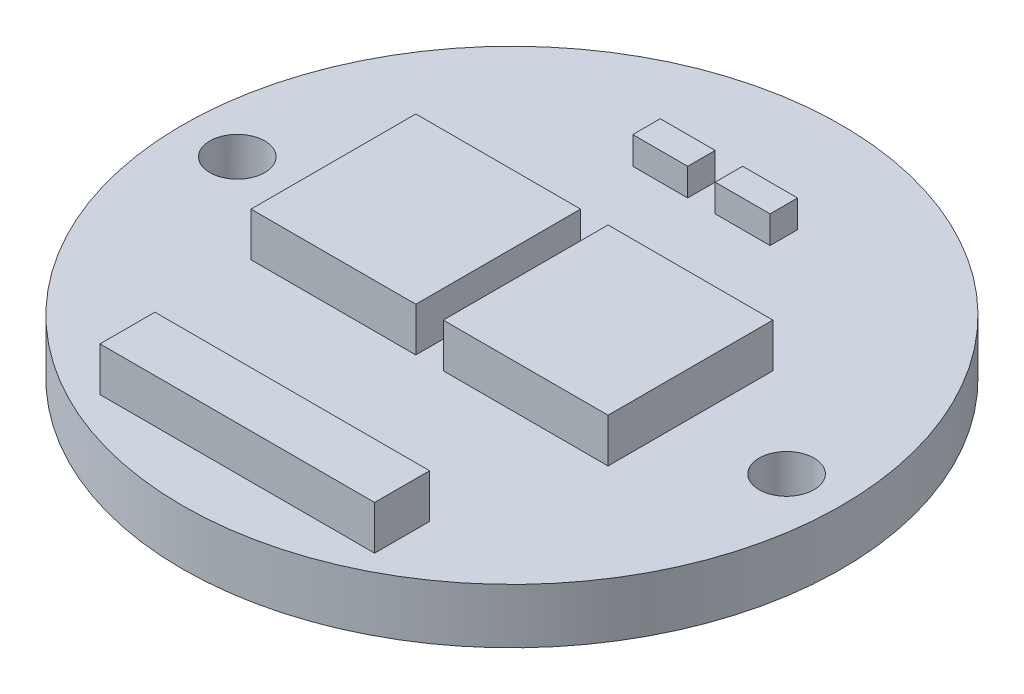
SolidWorks part; units mm, degrees
ref_plane "前视基准面" through (0, 0, 0) normal (0, 0, 1) x (1, 0, 0)
ref_plane "上视基准面" through (0, 0, 0) normal (0, 1, 0) x (1, 0, 0)
ref_plane "右视基准面" through (0, 0, 0) normal (1, 0, 0) x (0, 0, -1)
sketch "草图1" plane through (0, 0, 0) normal (0, 1, 0) x (1, 0, 0)
  circle A0 centre (0, 0) radius 6
extrude "凸台-拉伸1" add sketch "草图1" along normal blind 1
sketch "草图2" plane through (0, 1, 0) normal (0, 1, 0) x (1, 0, 0)
  line L0 (0, 6) -> (0, -6) construction
  line L1 (-0.25, -1.5) -> (-3.25, 1.5) construction
  line L2 (0.25, 1.5) -> (3.25, 1.5)
  line L3 (0.25, 1.5) -> (0.25, -1.5)
  line L4 (0.25, -1.5) -> (3.25, -1.5)
  line L5 (3.25, 1.5) -> (3.25, -1.5)
  line L6 (0.25, 1.5) -> (3.25, -1.5) construction
  line L7 (0.25, -1.5) -> (3.25, 1.5) construction
  line L8 (-0.25, 1.5) -> (-3.25, -1.5) construction
  line L9 (-3.25, 1.5) -> (-3.25, -1.5)
  line L10 (-0.25, -1.5) -> (-3.25, -1.5)
  line L11 (-0.25, 1.5) -> (-0.25, -1.5)
  line L12 (-0.25, 1.5) -> (-3.25, 1.5)
  line L13 (-0.25, 3.95) -> (-1.25, 3.45) construction
  line L14 (-2.5, -4) -> (2.5, -4)
  line L15 (-2.5, -4) -> (-2.5, -5)
  line L16 (-2.5, -5) -> (2.5, -5)
  line L17 (2.5, -4) -> (2.5, -5)
  line L18 (-2.5, -4) -> (2.5, -5) construction
  line L19 (-2.5, -5) -> (2.5, -4) construction
  line L20 (0.25, 3.45) -> (1.25, 3.45)
  line L21 (0.25, 3.45) -> (0.25, 3.95)
  line L22 (0.25, 3.95) -> (1.25, 3.95)
  line L23 (1.25, 3.45) -> (1.25, 3.95)
  line L24 (0.25, 3.45) -> (1.25, 3.95) construction
  line L25 (0.25, 3.95) -> (1.25, 3.45) construction
  line L26 (-0.25, 3.45) -> (-1.25, 3.95) construction
  line L27 (-1.25, 3.45) -> (-1.25, 3.95)
  line L28 (-0.25, 3.95) -> (-1.25, 3.95)
  line L29 (-0.25, 3.45) -> (-0.25, 3.95)
  line L30 (-0.25, 3.45) -> (-1.25, 3.45)
  circle A0 centre (0, 0) radius 6 construction
  point P5 (1.75, 0)
  point P10 (0.75, 3.7)
  point P16 (-1.75, 0)
  point P17 (0, -4.5)
  point P30 (-0.75, 3.7)
  dimension "D1" = 3
  dimension "D2" = 3
  dimension "D3" = 1.75
  dimension "D4" = 1
  dimension "D5" = 4.5
  dimension "D6" = 5
  dimension "D7" = 0.25
  dimension "D8" = 1
  dimension "D9" = 0.5
  dimension "D10" = 3.7
extrude "凸台-拉伸2" add sketch "草图2" along normal blind 0.8 contours L9 L10 L11 L12 | L3 L2 L5 L4 | L15 L14 L17 L16
extrude "凸台-拉伸3" add sketch "草图2<6>" along normal blind 0.5 contours L30 L29 L28 L27 | L20 L23 L22 L21 region at (0.75, 1, -3.7) region at (-0.75, 1, -3.7)
sketch "草图2<6>" plane through (0, 1, 0) normal (0, 1, 0) x (1, 0, 0) same geometry as "草图2"
sketch "草图4" plane through (0, 0, 0) normal (0, -1, 0) x (1, 0, 0)
  line L1 (-2.5, 2.5) -> (2.5, 2.5)
  line L2 (-2.5, 2.5) -> (-2.5, -2.5)
  line L3 (-2.5, -2.5) -> (2.5, -2.5)
  line L4 (2.5, 2.5) -> (2.5, -2.5)
  line L5 (-2.5, 2.5) -> (2.5, -2.5) construction
  line L6 (-2.5, -2.5) -> (2.5, 2.5) construction
  point P0 (0, 0)
  dimension "D1" = 5
  dimension "D2" = 5
extrude "凸台-拉伸4" add sketch "草图4" along normal blind 1
sketch "草图5" plane through (0, 1, 0) normal (0, 1, 0) x (1, 0, 0)
  line L0 (0, 0) -> (0, 6) construction
  circle A0 centre (5, 0) radius 0.5
  circle A2 centre (0, 0) radius 6 construction
  circle A3 centre (-5, 0) radius 0.5
  dimension "D1" = 5
  dimension "D2" = 1
extrude "切除-拉伸1" cut sketch "草图5" against normal up to next
sketch "草图6" plane through (0, 0, 5) normal (0, 0, 1) x (1, 0, 0)
  line L0 (-2.5, 1.8) -> (2.5, 1.8) construction
  point P0 (0, 1.4)
  dimension "D1" = 0.4
